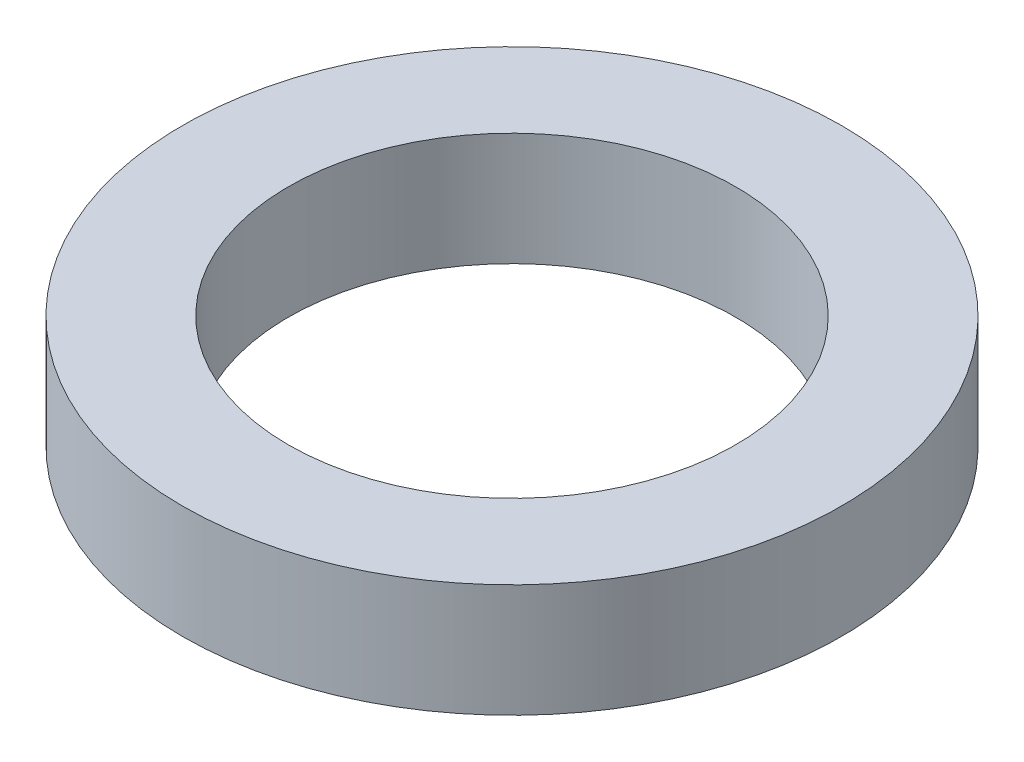
SolidWorks part; units mm, degrees
ref_plane "Front Plane" through (0, 0, 0) normal (0, 0, 1) x (1, 0, 0)
ref_plane "Top Plane" through (0, 0, 0) normal (0, 1, 0) x (1, 0, 0)
ref_plane "Right Plane" through (0, 0, 0) normal (1, 0, 0) x (0, 0, -1)
sketch "Sketch1" plane through (0, 0, 0) normal (0, 1, 0) x (1, 0, 0)
  circle A0 centre (0, 0) radius 70
  dimension "FLANGE_OD" = 140
extrude "Boss-Extrude1" add sketch "Sketch1" along normal blind 24
sketch "Sketch2" plane through (0, 0, 0) normal (0, 1, 0) x (1, 0, 0)
  circle A0 centre (0, 0) radius 47.5
  dimension "BORE_D" = 95
extrude "Cut-Extrude1" cut sketch "Sketch2" along normal through all
sketch "Sketch3" plane through (0, 24, 0) normal (0, 1, 0) x (1, 0, 0)
  circle A0 centre (0, 0) radius 30.5182 construction
  circle A1 centre (-30.5182, 0) radius 2.7327
  dimension "BOLT_D" = 5.4653
  dimension "BOLT_PCD" = 61.0363
extrude "Cut-Extrude2" cut sketch "Sketch3" against normal blind 22.1729 rebuild error yes
pattern_circular "CirPattern1" count 4 over 360 rebuild error yes
